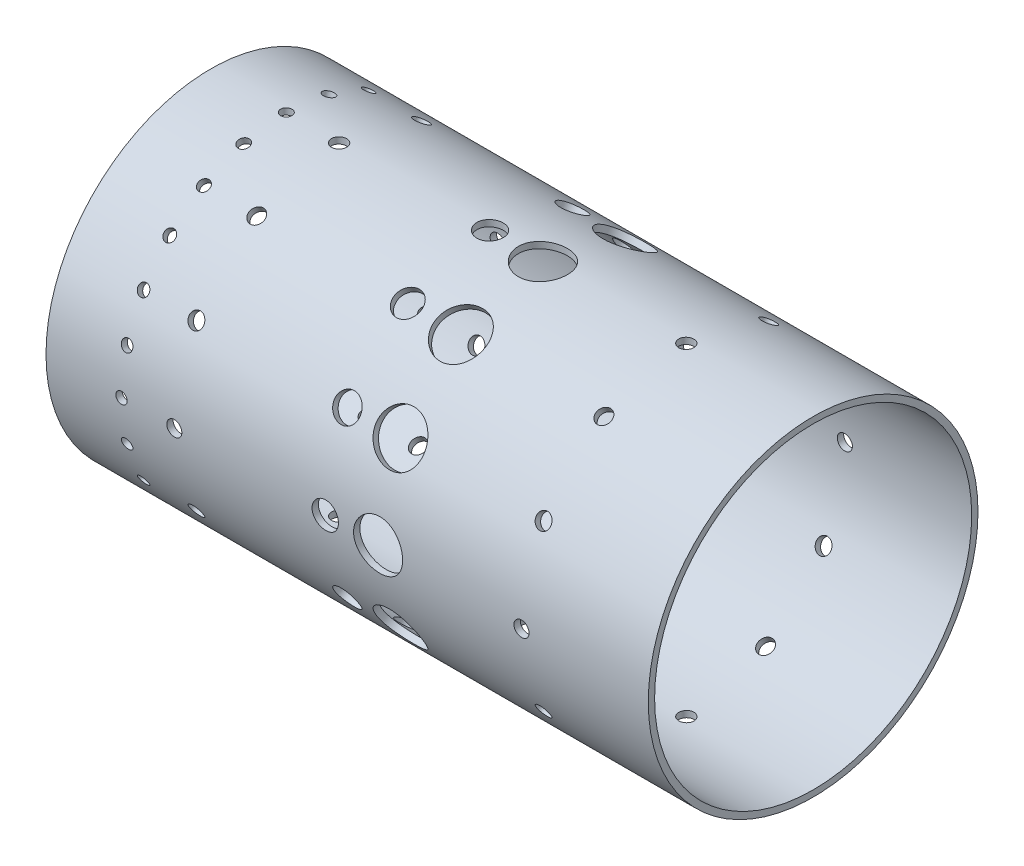
SolidWorks part; units mm, degrees
ref_plane "Front Plane" through (0, 0, 0) normal (0, 0, 1) x (1, 0, 0)
ref_plane "Top Plane" through (0, 0, 0) normal (0, 1, 0) x (1, 0, 0)
ref_plane "Right Plane" through (0, 0, 0) normal (1, 0, 0) x (0, 0, -1)
sketch "Sketch1" plane through (0, 0, 0) normal (1, 0, 0) x (0, 0, -1)
  circle A0 centre (0, 0) radius 21.0058
  circle A1 centre (0, 0) radius 21.844
  dimension "D1" = 43.688
  dimension "D2" = 0.8382
extrude "Boss-Extrude1" add sketch "Sketch1" along normal blind 79.8044
sketch "Sketch3" plane through (0, 0, 0) normal (0, 1, 0) x (1, 0, 0)
  line L0 (0, 0) -> (79.3536, 0) construction
sketch "Sketch4" plane through (0, 0, 0) normal (0, 1, 0) x (1, 0, 0)
  line L0 (0, 0) -> (79.3536, 0) construction
  circle A0 centre (10, 0) radius 0.75
  dimension "D2" = 1.5
  dimension "D1" = 10
extrude "Cut-Extrude1" cut sketch "Sketch4" against normal through all
pattern_circular "CirPattern1" count 24 over 360 about axis through (0, 0, 0) along (1, 0, 0) of "Cut-Extrude1"
sketch "Sketch5" plane through (0, 0, 0) normal (0, 1, 0) x (1, 0, 0)
  line L0 (0, 0) -> (79.3536, 0) construction
  line L1 (0, 21.844) -> (0, -21.844) construction
  circle A0 centre (17, 0) radius 1
  dimension "D2" = 2
  dimension "D1" = 17
extrude "Cut-Extrude3" cut sketch "Sketch5" against normal through all
pattern_circular "CirPattern2" count 12 over 360 about axis through (0, 0, 0) along (1, 0, 0) of "Cut-Extrude3"
sketch "Sketch6" plane through (0, 0, 0) normal (0, 1, 0) x (1, 0, 0)
  line L0 (0, 0) -> (79.3536, 0) construction
  line L1 (0, 21.844) -> (0, -21.844) construction
  circle A0 centre (37, 0) radius 1.75
  dimension "D2" = 3.5
  dimension "D1" = 37
extrude "Cut-Extrude4" cut sketch "Sketch6" against normal through all
pattern_circular "CirPattern3" count 12 over 360 about axis through (0, 0, 0) along (1, 0, 0) of "Cut-Extrude4"
sketch "Sketch7" plane through (0, 0, 0) normal (0, 1, 0) x (1, 0, 0)
  line L0 (0, 0) -> (79.3536, 0) construction
  circle A0 centre (44, 0) radius 3.25
  dimension "D2" = 6.5
  dimension "D1" = 44
extrude "Cut-Extrude5" cut sketch "Sketch7" against normal through all
pattern_circular "CirPattern5" count 12 over 360 about axis through (0, 0, 0) along (1, 0, 0) of "Cut-Extrude5" reverse direction yes
sketch "Sketch8" plane through (0, 0, 0) normal (0, 0, 1) x (1, 0, 0)
  line L0 (0, 0) -> (79.3536, 0) construction
  circle A0 centre (63, 0) radius 1
  dimension "D1" = 2
  dimension "D2" = 63
extrude "Cut-Extrude6" cut sketch "Sketch8" against normal through all
pattern_circular "CirPattern6" count 12 over 360 about axis through (0, 0, 0) along (1, 0, 0) of "Cut-Extrude6" reverse direction yes
